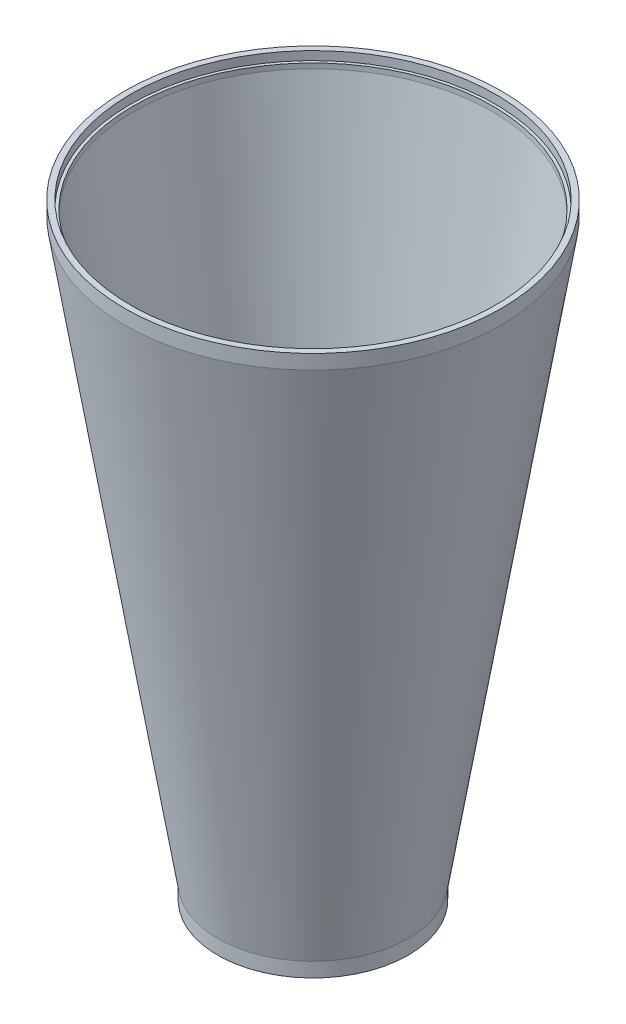
SolidWorks part; units mm, degrees
ref_plane "정면" through (0, 0, 0) normal (0, 0, 1) x (1, 0, 0)
ref_plane "윗면" through (0, 0, 0) normal (0, 1, 0) x (1, 0, 0)
ref_plane "우측면" through (0, 0, 0) normal (1, 0, 0) x (0, 0, -1)
sketch "스케치1" plane through (0, 0, 0) normal (0, 0, 1) x (1, 0, 0)
  line L0 (0, 0) -> (65.2, 0)
  line L1 (65.2, 0) -> (33, -200)
  line L2 (33, -200) -> (33, -205)
  line L3 (33, -205) -> (0, -205)
  line L4 (0, -205) -> (0, 0)
  dimension "D1" = 65.2
  dimension "D2" = 5
  dimension "D3" = 33
  dimension "D4" = 200
revolve "회전1" add sketch "스케치1" angle 360 about L4
sketch "스케치3" plane through (0, 0, 0) normal (0, 1, 0) x (1, 0, 0)
  circle A1 centre (0, 0) radius 65.2
  circle A2 centre (0, 0) radius 65.2
  dimension "D1" = 0
extrude "보스-돌출2" add sketch "스케치3" along normal blind 5
shell "쉘1" thickness 3 removed face at (33, -205, 0) removed face at (-65.2, 5, 0)
sketch "스케치4" plane through (0, 5, 0) normal (0, 1, 0) x (1, 0, 0)
  circle A2 centre (0, 0) radius 63.2
  circle A4 centre (0, 0) radius 62.2 construction
  circle A5 centre (0, 0) radius 65.2
  circle A6 centre (0, 0) radius 65.2
  circle A7 centre (0, 0) radius 62.2
  circle M3 centre (0, 0) radius 62.2
  dimension "D1" = 126.4
  dimension "D2" = 0
extrude "컷-돌출3" cut sketch "스케치4" against normal blind 3 contours A2 M3 region at (-63.0212, 5, 0)
sketch "스케치7" plane through (0, -205, 0) normal (0, -1, 0) x (1, 0, 0)
  circle A0 centre (0, 0) radius 31
  circle A1 centre (0, 0) radius 33
  circle A2 centre (0, 0) radius 33
  circle A3 centre (0, 0) radius 30 construction
  circle A4 centre (0, 0) radius 30
  circle M3 centre (0, 0) radius 30
  dimension "D2" = 62
  dimension "D1" = 0
extrude "컷-돌출6" cut sketch "스케치7" against normal blind 3 contours A0 M3 region at (-30.1232, -205, 0)
